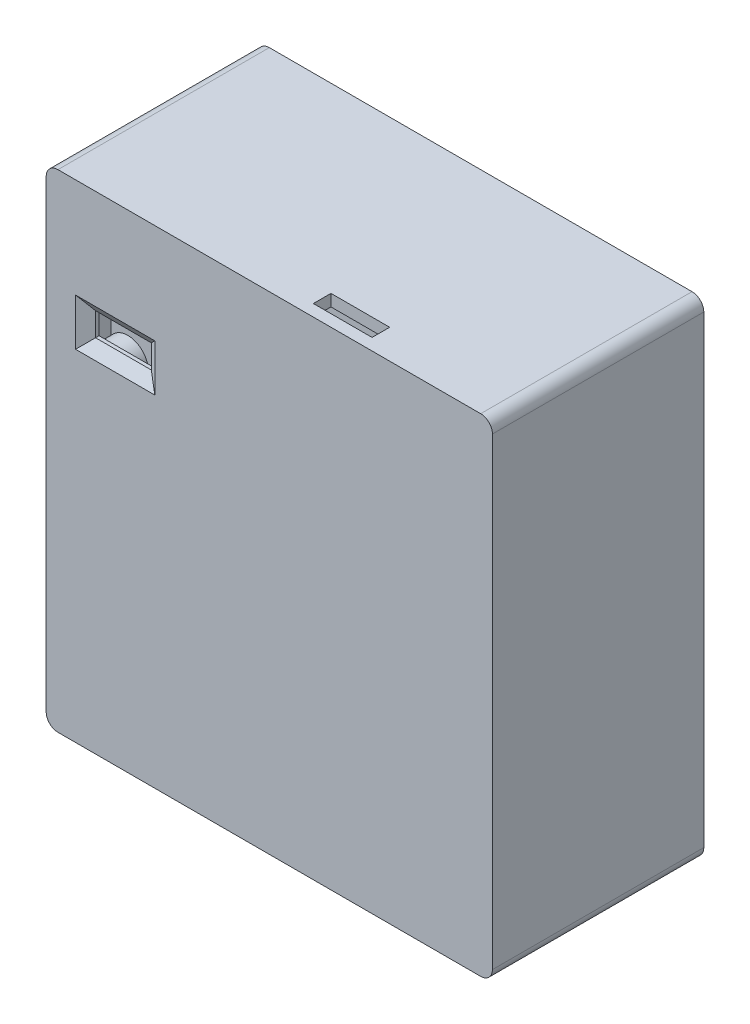
SolidWorks part; units mm, degrees
ref_plane "Front Plane" through (0, 0, 0) normal (0, 0, 1) x (1, 0, 0)
ref_plane "Top Plane" through (0, 0, 0) normal (0, 1, 0) x (1, 0, 0)
ref_plane "Right Plane" through (0, 0, 0) normal (1, 0, 0) x (0, 0, -1)
sketch "Sketch1" plane through (0, 0, 0) normal (0, 1, 0) x (1, 0, 0)
  line L0 (-38, 18) -> (38, 18)
  line L1 (-36, -16) -> (36, -16)
  line L2 (-36, -16) -> (-36, 16)
  line L3 (-36, 16) -> (36, 16)
  line L4 (36, -16) -> (36, 16)
  line L5 (-36, -16) -> (36, 16) construction
  line L6 (-36, 16) -> (36, -16) construction
  line L7 (38, -18) -> (38, 18)
  line L8 (-38, -18) -> (38, -18)
  line L9 (-38, -18) -> (-38, 18)
  point P0 (0, 0)
  dimension "D1" = 32
  dimension "D2" = 72
  dimension "D3" = 2
extrude "Boss-Extrude2" add sketch "Sketch1" along normal blind 39.5 and the other way blind 39.5
sketch "Sketch2" plane through (0, -39.5, 0) normal (0, -1, 0) x (1, 0, 0)
  line L1 (-38, -18) -> (38, -18)
  line L2 (-38, -18) -> (-38, 18)
  line L3 (-38, 18) -> (38, 18)
  line L4 (38, -18) -> (38, 18)
  line L5 (-38, -18) -> (38, 18) construction
  line L6 (-38, 18) -> (38, -18) construction
  point P0 (0, 0)
extrude "Boss-Extrude3" add sketch "Sketch2" along normal blind 2
mirror "Mirror1" about plane through (0, 0, 0) normal (0, 1, 0) of "Boss-Extrude3"
sketch "Sketch6" plane through (0, 0, 0) normal (0, 0, 1) x (1, 0, 0)
  line L1 (-35, -31.5) -> (35, -31.5)
  line L2 (-35, -31.5) -> (-35, 38.5)
  line L3 (-35, 38.5) -> (35, 38.5)
  line L4 (35, -31.5) -> (35, 38.5)
  line L5 (-35, -31.5) -> (35, 38.5) construction
  line L6 (-35, 38.5) -> (35, -31.5) construction
  line L7 (36, 39.5) -> (-36, 39.5) construction
  point P0 (0, 3.5)
  dimension "D1" = 70
  dimension "D2" = 70
  dimension "D3" = 1
extrude "Boss-Extrude4" add sketch "Sketch6" along normal blind 10 and the other way blind 10
fillet "Fillet1" radius 2 4 edges at (-38, 41.5, 0) (-38, -41.5, 0) (38, -41.5, 0) (38, 41.5, 0)
ref_plane "Plane1" through (0, 0, 16) normal (0, 0, 1) x (1, 0, 0)
sketch "Sketch7" plane through (0, 0, 16) normal (0, 0, 1) x (1, 0, 0)
  line L1 (-38, -17) -> (-36, -17)
  line L2 (-38, -17) -> (-38, -7)
  line L3 (-38, -7) -> (-36, -7)
  line L4 (-36, -17) -> (-36, -7)
  line L5 (-36, -39.5) -> (-36, 39.5) construction
  line L6 (-36, 41.5) -> (36, 41.5) construction
  line L7 (5.5, 41.5) -> (15.5, 41.5)
  line L8 (5.5, 41.5) -> (5.5, 39.5)
  line L9 (5.5, 39.5) -> (15.5, 39.5)
  line L10 (15.5, 41.5) -> (15.5, 39.5)
  line L11 (36, 39.5) -> (-36, 39.5) construction
  line L12 (-35, 38.5) -> (-35, -31.5) construction
  dimension "D1" = 10
  dimension "D2" = 10
  dimension "D3" = 40.5
  dimension "D4" = 7
  dimension "D5" = 2
extrude "Cut-Extrude1" cut sketch "Sketch7" against normal blind 3
sketch "Sketch8" plane through (-38, 0, 0) normal (-1, 0, 0) x (0, 0, 1)
  circle A0 centre (-6, 8) radius 6.5
  dimension "D1" = 13
  dimension "D2" = 6
  dimension "D3" = 8
extrude "Cut-Extrude2" cut sketch "Sketch8" against normal up to next (2 mm away)
sketch "Sketch9" plane through (0, 0, -16) normal (0, 0, 1) x (1, 0, 0)
  line L1 (-26.5, 20) -> (-6.5, 20)
  line L2 (-26.5, 20) -> (-26.5, 27)
  line L3 (-26.5, 27) -> (-6.5, 27)
  line L4 (-6.5, 20) -> (-6.5, 27)
  line L5 (-26.5, -27.5) -> (-1.5, -27.5)
  line L6 (-26.5, -27.5) -> (-26.5, -20.5)
  line L7 (-26.5, -20.5) -> (-1.5, -20.5)
  line L8 (-1.5, -27.5) -> (-1.5, -20.5)
  line L9 (-6.5, 20) -> (-6.5, -20.5) construction
  line L10 (8, 9.75) -> (1, 9.75)
  line L11 (8, 9.75) -> (8, -10.25)
  line L12 (8, -10.25) -> (1, -10.25)
  line L13 (1, 9.75) -> (1, -10.25)
  line L14 (-36, -39.5) -> (-36, 39.5) construction
  point P10 (1, -0.25)
  point P12 (-6.5, -0.25)
  dimension "D1" = 40.5
  dimension "D2" = 7
  dimension "D3" = 7
  dimension "D4" = 20
  dimension "D5" = 25
  dimension "D6" = 20
  dimension "D7" = 7
  dimension "D8" = 20
  dimension "D9" = 27.5
  dimension "D10" = 9.5
extrude "Boss-Extrude5" add sketch "Sketch9" along normal blind 10
sketch "Sketch10" plane through (0, 0, 18) normal (0, 0, 1) x (1, 0, 0)
  line L0 (36, 41.5) -> (-36, 41.5) construction
  line L1 (-21.5, 22.5) -> (-31, 22.5)
  line L2 (-21.5, 22.5) -> (-21.5, 18.5)
  line L3 (-21.5, 18.5) -> (-31, 18.5)
  line L4 (-31, 22.5) -> (-31, 18.5)
  line L5 (-38, -39.5) -> (-38, 39.5) construction
  dimension "D1" = 4
  dimension "D2" = 9.5
  dimension "D3" = 19
  dimension "D4" = 7
extrude "Cut-Extrude3" cut sketch "Sketch10" against normal up to next (2 mm away)
chamfer "Chamfer1" distance 2 angle 35 4 edges at (-31, 20.5, 18) (-26.25, 22.5, 18) (-26.25, 18.5, 18) (-21.5, 20.5, 18) first distance on face at (-26.25, 20.5, 18)
sketch "Sketch11" plane through (0, 0, 16) normal (0, 0, -1) x (-1, 0, 0)
  line L1 (-36, -39.5) -> (-36, 39.5) construction
  line L2 (36, -39.5) -> (-36, -39.5) construction
  circle A0 centre (32.1, 11.5) radius 3.5
  circle A1 centre (-32.4, -33.5) radius 3.5
  circle A2 centre (-32.4, 11.5) radius 3.5
  circle A3 centre (32.1, 11.5) radius 1.5
  circle A4 centre (-32.4, 11.5) radius 1.5
  circle A5 centre (-32.4, -33.5) radius 1.5
  dimension "D1" = 7
  dimension "D2" = 7
  dimension "D3" = 7
  dimension "D4" = 6
  dimension "D5" = 3.6
  dimension "D6" = 45
  dimension "D7" = 64.5
  dimension "D8" = 2
extrude "Boss-Extrude10" add sketch "Sketch11" along normal blind 7.3
